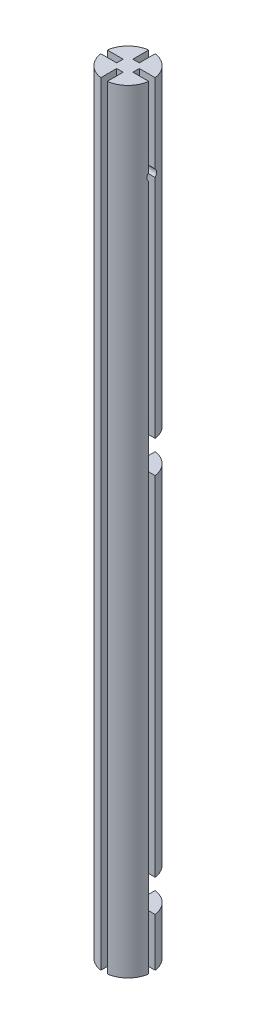
SolidWorks part; units mm, degrees
ref_plane "Front Plane" through (0, 0, 0) normal (0, 0, 1) x (1, 0, 0)
ref_plane "Top Plane" through (0, 0, 0) normal (0, 1, 0) x (1, 0, 0)
ref_plane "Right Plane" through (0, 0, 0) normal (1, 0, 0) x (0, 0, -1)
sketch "Sketch1" plane through (0, 0, 0) normal (0, 1, 0) x (1, 0, 0)
  line L5 (0, 194.8226) -> (0, 75) construction
  line L18 (-10, 74.3303) -> (-10, 25)
  line L19 (-10, 25) -> (10, 25)
  line L20 (10, 74.3303) -> (10, 25)
  line L21 (-29.2048, 0) -> (25.2155, 0) construction
  line L22 (74.3303, -10) -> (25, -10)
  line L23 (74.3303, 10) -> (25, 10)
  line L24 (25, 10) -> (25, -10)
  line L25 (-10, -74.3303) -> (-10, -25)
  line L26 (10, -74.3303) -> (10, -25)
  line L27 (10, -25) -> (-10, -25)
  line L28 (-74.3303, 10) -> (-25, 10)
  line L29 (-74.3303, -10) -> (-25, -10)
  line L30 (-25, -10) -> (-25, 10)
  line L31 (0, 75) -> (0, 25) construction
  line L32 (0, 25) -> (0, -243.8201) construction
  arc A2 (-10, 74.3303) -> (-74.3303, 10) centre (0, 0) ccw
  arc A3 (-74.3303, -10) -> (-10, -74.3303) centre (0, 0) ccw
  arc A4 (10, -74.3303) -> (74.3303, -10) centre (0, 0) ccw
  arc A5 (74.3303, 10) -> (10, 74.3303) centre (0, 0) ccw
  arc A6 (-10, 74.3303) -> (29.2889, 69.0446) centre (0, 0) cw
  point P1 (0, 25)
  point P4 (0, 93.7498)
  point P24 (-100, 0)
  point P29 (0, 0)
  point P30 (0, 0)
  dimension "D1" = 150
  dimension "D2" = 20
  dimension "D3" = 50
  dimension "D4" = 4
extrude "Boss-Extrude2" add sketch "Sketch1" along normal blind 4000 contours A2 L28 L30 L29 A3 L25 L27 L26 A4 L22 L24 L23 A5 L20 L19 L18
sketch "Sketch2" plane through (0, 0, 0) normal (0, 1, 0) x (1, 0, 0)
  line L0 (0, 74.3303) -> (0, 0)
  line L1 (74.3303, 74.3303) -> (74.3303, 0)
  line L2 (74.3303, 74.3303) -> (0, 74.3303)
  line L3 (74.3303, 0) -> (0, 0)
extrude "Cut-Extrude1" cut sketch "Sketch2" along normal mid plane 100 from offset 200
extrude "Cut-Extrude2" cut sketch "Sketch2<2>" against normal mid plane 100 from offset 1380
sketch "Sketch2<2>" plane through (0, 0, 0) normal (0, 1, 0) x (1, 0, 0) same geometry as "Sketch2"
ref_plane "Plane1" through (74.3303, 0, 0) normal (1, 0, 0) x (0, 0, -1)
ref_plane "Plane2" through (0, 0, -74.3303) normal (0, 0, -1) x (-1, 0, 0)
sketch "Sketch3" plane through (74.3303, 0, 0) normal (1, 0, 0) x (0, 0, -1)
  circle A0 centre (0, 2143) radius 15.2
extrude "Cut-Extrude3" cut sketch "Sketch3" against normal up to surface (49.3303 mm away) up to face at (25, 1193.3333, -3.3333)
sketch "Sketch4" plane through (0, 0, -74.3303) normal (0, 0, -1) x (-1, 0, 0)
  circle A2 centre (0, 2143) radius 15.2
extrude "Cut-Extrude4" cut sketch "Sketch4" against normal up to surface (49.3303 mm away) up to face at (3.3333, 1193.3333, -25)
sketch "Sketch5" plane through (0, 0, 25) normal (0, 0, 1) x (1, 0, 0)
  line L0 (-74.3303, 4000) -> (-74.3303, 2400)
  line L9 (-74.3303, 4000) -> (-74.3303, 0) construction
  line L10 (-74.3303, 2400) -> (74.3303, 2400)
  line L11 (74.3303, -16.72) -> (74.3303, 16.72) construction
  line L12 (74.3303, 2400) -> (74.3303, 4000)
  line L13 (74.3303, 4000) -> (74.3303, 2154.4473) construction
  line L14 (-74.3303, 4000) -> (74.3303, 4000)
extrude "Cut-Extrude5" cut sketch "Sketch5" against normal through all both and the other way through all
